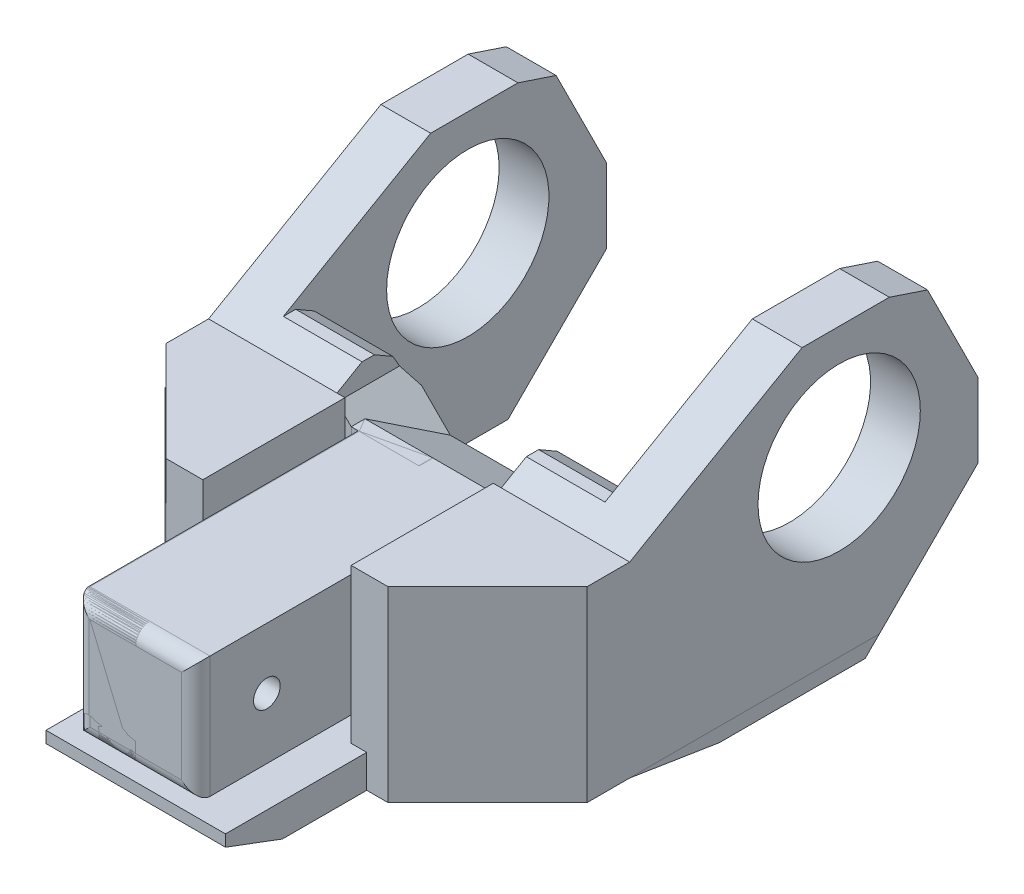
SolidWorks part; units mm, degrees
note: The reader was unsure of these and kept them because the rebuilt part matched: shared geometry of "Sketch1<4>".
ref_plane "Front Plane" through (0, 0, 0) normal (0, 0, 1) x (1, 0, 0)
ref_plane "Top Plane" through (0, 0, 0) normal (0, 1, 0) x (1, 0, 0)
ref_plane "Right Plane" through (0, 0, 0) normal (1, 0, 0) x (0, 0, -1)
sketch "Sketch1" plane through (0, 0, 0) normal (0, 1, 0) x (1, 0, 0)
  line L2 (0, 0) -> (0, 40)
  line L3 (0, 40) -> (21.59, 40)
  line L4 (21.59, 0) -> (21.59, 40)
  line L5 (-1.5, 40) -> (23.09, 40)
  line L6 (-1.5, 40) -> (-1.5, 45)
  line L7 (-1.5, 45) -> (23.09, 45)
  line L8 (23.09, 40) -> (23.09, 45)
  line L10 (0, 0) -> (0, -10.6333)
  line L11 (0, -10.6333) -> (21.59, -10.6333)
  line L12 (21.59, 0) -> (21.59, -10.6333)
  dimension "D1" = 21.59
  dimension "D3" = 1.5
  dimension "D4" = 1.5
  dimension "D5" = 5
extrude "Boss-Extrude1" add sketch "Sketch1" along normal blind 21.73
extrude "Boss-Extrude2" add sketch "Sketch1<4>" against normal blind 1.5 and the other way blind 23.23 contours L5 L8 L7 L6 L3
sketch "Sketch1<4>" plane through (0, 0, 0) normal (0, 1, 0) x (1, 0, 0) same geometry as "Sketch1"
sketch "Sketch2" plane through (23.09, 0, 0) normal (1, 0, 0) x (0, 0, -1)
  line L0 (40, -1.5) -> (45, -1.5) construction
  line L1 (40, 23.23) -> (59.05, 23.23)
  line L2 (40, 23.23) -> (40, -1.5)
  line L3 (40, -1.5) -> (59.05, -1.5)
  line L4 (59.05, 23.23) -> (59.05, -1.5)
  dimension "D1" = 19.05
extrude "Boss-Extrude3" add sketch "Sketch2" along normal blind 25.4
sketch "Sketch3" plane through (0, 0, -59.05) normal (0, 0, -1) x (-1, 0, 0)
  line L0 (-48.49, -1.5) -> (-23.09, -1.5) construction
  line L1 (-48.49, 23.23) -> (-42.14, 23.23)
  line L2 (-48.49, 23.23) -> (-48.49, -1.5)
  line L3 (-48.49, -1.5) -> (-42.14, -1.5)
  line L4 (-42.14, 23.23) -> (-42.14, -1.5)
  dimension "D1" = 6.35
extrude "Boss-Extrude4" add sketch "Sketch3" along normal blind 43.18
sketch "Sketch4" plane through (0, 0, -59.05) normal (0, 0, -1) x (-1, 0, 0)
  line L1 (-42.14, -1.5) -> (-23.09, -1.5)
  line L2 (-42.14, -1.5) -> (-42.14, 23.23)
  line L3 (-42.14, 23.23) -> (-23.09, 23.23)
  line L4 (-23.09, -1.5) -> (-23.09, 23.23)
extrude "Cut-Extrude1" cut sketch "Sketch4" against normal up to vertex (14.05 mm away)
sketch "Sketch5" plane through (0, 0, -45) normal (0, 0, -1) x (-1, 0, 0)
  line L1 (-42.14, 23.23) -> (1.5, 23.23)
  line L2 (-42.14, 23.23) -> (-42.14, -1.5)
  line L3 (-42.14, -1.5) -> (1.5, -1.5)
  line L4 (1.5, 23.23) -> (1.5, -1.5)
extrude "Boss-Extrude5" add sketch "Sketch5" along normal blind 7.62
sketch "Sketch6" plane through (0, -1.5, 0) normal (0, -1, 0) x (1, 0, 0)
  line L0 (48.49, -40) -> (48.49, -102.23) construction
  line L1 (-1.5, -40) -> (48.49, -40)
  line L2 (-1.5, -40) -> (-1.5, -52.62)
  line L3 (-1.5, -52.62) -> (42.14, -52.62)
  line L4 (48.49, -40) -> (48.49, -46.27)
  line L6 (48.49, -102.23) -> (42.14, -102.23)
  line L7 (48.49, -102.23) -> (48.49, -46.27)
  line L9 (42.14, -102.23) -> (42.14, -52.62)
extrude "Boss-Extrude6" add sketch "Sketch6" along normal blind 8.79
sketch "Sketch7" plane through (0, 23.23, 0) normal (0, 1, 0) x (1, 0, 0)
  line L0 (48.49, 102.23) -> (48.49, 40) construction
  line L1 (-1.5, 40) -> (48.49, 40)
  line L2 (-1.5, 40) -> (-1.5, 52.62)
  line L3 (-1.5, 52.62) -> (42.14, 52.62)
  line L4 (48.49, 40) -> (48.49, 46.27)
  line L5 (-1.5, 52.62) -> (42.14, 52.62) construction
  line L7 (42.14, 102.23) -> (48.49, 102.23)
  line L8 (42.14, 102.23) -> (42.14, 52.62)
  line L10 (48.49, 102.23) -> (48.49, 46.27)
extrude "Boss-Extrude7" add sketch "Sketch7" along normal blind 20.22
sketch "Sketch9" plane through (42.14, 0, 0) normal (-1, 0, 0) x (0, 0, 1)
  line L1 (-102.23, 43.45) -> (-52.62, 43.45)
  line L2 (-102.23, 43.45) -> (-102.23, -10.29)
  line L3 (-102.23, -10.29) -> (-52.62, -10.29)
  line L4 (-52.62, 43.45) -> (-52.62, -10.29)
extrude "Boss-Extrude8" add sketch "Sketch9" along normal blind 2.54
sketch "Sketch10" plane through (39.6, 0, 0) normal (-1, 0, 0) x (0, 0, 1)
  line L0 (-77.425, 43.45) -> (-77.425, 23.13)
  line L1 (-52.62, 43.45) -> (-102.23, 43.45) construction
  circle A0 centre (-77.425, 23.13) radius 14.5
  dimension "D1" = 29
  dimension "D2" = 20.32
extrude "Cut-Extrude2" cut sketch "Sketch10" against normal blind 44.704
sketch "Sketch11" plane through (0, 0, 10.6333) normal (0, 0, 1) x (1, 0, 0)
  line L6 (0, 0) -> (21.59, 0) construction
  line L7 (0, 21.73) -> (0, 0) construction
  circle A0 centre (2.54, 2.54) radius 1.778
  dimension "D1" = 3.556
  dimension "D3" = 2.54
  dimension "D2" = 2.54
fillet "Fillet3" radius 2.54 4 edges at (10.795, 0, 10.6333) (0, 10.865, 10.6333) (10.795, 21.73, 10.6333) (21.59, 10.865, 10.6333)
chamfer "Chamfer1" distance 20.16 angle 45 1 edges at (44.045, -10.29, -102.23)
chamfer "Chamfer2" distance 20.32 distance2 10.16 1 edges at (44.045, 43.45, -102.23)
sketch "Sketch12" plane through (0, 0, -40) normal (0, 0, 1) x (1, 0, 0)
  line L0 (-1.5, 43.45) -> (-1.5, -10.29) construction
  line L1 (-1.5, 21.73) -> (21.73, 21.73)
  line L2 (-1.5, 21.73) -> (-1.5, 43.45)
  line L3 (-1.5, 43.45) -> (21.73, 43.45)
  line L4 (21.73, 21.73) -> (21.73, 43.45)
  line L5 (-1.5, 43.45) -> (48.49, 43.45) construction
extrude "Cut-Extrude4" cut sketch "Sketch12" against normal blind 23.114
sketch "Sketch13" plane through (21.73, 0, 0) normal (-1, 0, 0) x (0, 0, 1)
  line L1 (-52.62, 43.45) -> (-40, 43.45)
  line L2 (-52.62, 43.45) -> (-52.62, 21.73)
  line L3 (-52.62, 21.73) -> (-40, 21.73)
  line L4 (-40, 43.45) -> (-40, 21.73)
extrude "Cut-Extrude5" cut sketch "Sketch13" against normal blind 3.81
chamfer "Chamfer4" distance 2.54 angle 45 1 edges at (25.54, 21.73, -46.31)
chamfer "Chamfer7" distance 17.78 angle 60 1 edges at (37.015, 43.45, -40)
chamfer "Chamfer8" distance 2.54 angle 81 1 edges at (23.495, -10.29, -40)
chamfer "Chamfer10" distance 12.7 distance2 6.35 1 edges at (39.6, 11.6037, -52.62)
sketch "Sketch16" plane through (0, 0, -40) normal (0, 0, 1) x (1, 0, 0)
  line L0 (-1.5, -7.75) -> (48.49, -7.75) construction
  line L1 (48.49, 25.67) -> (26.9, 25.67)
  line L2 (48.49, 25.67) -> (48.49, -7.75)
  line L3 (48.49, -7.75) -> (26.9, -7.75)
  line L4 (26.9, 25.67) -> (26.9, -7.75)
  dimension "D1" = 21.59
extrude "Boss-Extrude9" add sketch "Sketch16" along normal blind 25.4
sketch "Sketch17" plane through (-1.5, 0, 0) normal (-1, 0, 0) x (0, 0, 1)
  line L0 (-52.62, 21.73) -> (-52.62, -9.7488)
  line L1 (-52.62, -9.7488) -> (-40, -7.75)
  line L2 (-40, -7.75) -> (-40, 21.73)
  line L3 (-40, 21.73) -> (-52.62, 21.73)
extrude "Boss-Extrude10" add sketch "Sketch17" along normal blind 25.4
chamfer "Chamfer12" distance 5.08 distance2 10.16 1 edges at (-1.95, 21.73, -52.62)
chamfer "Chamfer13" distance 2.54 angle 45 1 edges at (44.045, 43.45, -92.07)
sketch "Sketch18" plane through (0, 0, -40) normal (0, 0, 1) x (1, 0, 0)
  line L0 (-26.9, 21.73) -> (0, 21.73) construction
  line L1 (-26.9, -7.75) -> (-2.77, -7.75)
  line L2 (-26.9, -7.75) -> (-26.9, 21.73)
  line L3 (-26.9, 21.73) -> (-2.77, 21.73)
  line L4 (-2.77, -7.75) -> (-2.77, 21.73)
  dimension "D1" = 24.13
extrude "Boss-Extrude11" add sketch "Sketch18" along normal blind 25.4
extrude "Cut-Extrude9" cut sketch "Sketch11" against normal through all
chamfer "Chamfer14" distance 17.78 angle 45 2 edges at (48.49, 8.96, -14.6) (-26.9, 6.99, -14.6)
sketch "Sketch19" plane through (0, 0, -40) normal (0, 0, 1) x (1, 0, 0)
  line L0 (26.9, 25.67) -> (26.9, -7.75) construction
  line L1 (-2.77, -7.75) -> (26.9, -7.75)
  line L2 (-2.77, -7.75) -> (-2.77, -2.67)
  line L3 (-2.77, -2.67) -> (26.9, -2.67)
  line L4 (26.9, -7.75) -> (26.9, -2.67)
  dimension "D1" = 5.08
extrude "Boss-Extrude12" add sketch "Sketch19" along normal through all
chamfer "Chamfer15" distance 10.16 distance2 3.81 1 edges at (12.065, -7.75, 10.6333)
sketch "Sketch20" plane through (0, 0, 0) normal (-1, 0, 0) x (0, 0, 1)
  line L0 (8.0933, 21.73) -> (-2.0667, 21.73)
  line L1 (8.0933, 21.73) -> (-40, 21.73) construction
  line L2 (-2.0667, 21.73) -> (-2.0667, 10.865)
  line L3 (-2.0667, 10.865) -> (8.0933, 10.865)
  line L4 (8.0933, 0) -> (8.0933, 21.73) construction
  circle A0 centre (-2.0667, 10.865) radius 2.3812
  dimension "D1" = 4.7625
  dimension "D2" = 10.16
extrude "Cut-Extrude10" cut sketch "Sketch20" against normal through all contours L2 A0 L3 | L3 A0 L2
sketch "Sketch21" plane through (0, 0, -40) normal (0, 0, -1) x (-1, 0, 0)
  line L1 (2.77, 21.73) -> (26.9, 21.73)
  line L2 (2.77, 21.73) -> (2.77, 18.7814)
  line L3 (2.77, 18.7814) -> (26.9, 18.7814)
  line L4 (26.9, 21.73) -> (26.9, 18.7814)
extrude "Cut-Extrude11" cut sketch "Sketch21" against normal up to surface (25.4 mm away) up to face at (-5.31, 5.058, -14.6)
sketch "Sketch22" plane through (-26.9, 0, 0) normal (-1, 0, 0) x (0, 0, 1)
  line L0 (-40, 18.7814) -> (-52.62, 10.0359)
  line L1 (-52.62, 16.65) -> (-52.62, -9.7488) construction
  line L2 (-52.62, 10.0359) -> (-52.62, 16.65)
  line L3 (-52.62, 16.65) -> (-40, 18.7814)
extrude "Cut-Extrude12" [suppressed] cut sketch "Sketch22" against normal up to surface (50.13 mm away)
ref_plane "Plane2" through (0, -7.75, 0) normal (0, -1, 0) x (-1, 0, 0)
split "Split1" trim tools "Plane2" bodies to split 124 resulting bodies 126 127
sketch "Sketch23" plane through (0, 21.73, 0) normal (0, 1, 0) x (1, 0, 0)
  line L0 (10.795, -8.0933) -> (10.795, 44.5675)
  line L1 (0, -8.0933) -> (21.59, -8.0933) construction
  line L2 (23, 50.67) -> (6.58, 42.46) construction
split line "Split Line1"
ref_plane "Plane3" through (10.865, 0, 0) normal (-1, 0, 0) x (0, 0, 1)
split "Split2" trim tools "Plane3" bodies to split 128 resulting bodies 129 130
mirror "Mirror2" about plane through (10.865, 0, 0) normal (-1, 0, 0) of bodies 129
combine bodies "Combine1" operation type add bodies to combine 131 129
sketch "Sketch24" plane through (0, 1.932, 1.1154) normal (0, 0.866, 0.5) x (1, 0, 0)
  line L0 (-3.81, 62.0483) -> (-3.81, 56.4603)
  line L1 (-3.81, 47.476) -> (-3.81, 62.0483) construction
  line L2 (-3.81, 56.4603) -> (-17.87, 56.4603)
  line L3 (-17.87, 56.4603) -> (-17.87, 69.3807)
  line L4 (-17.87, 69.3807) -> (-5.17, 62.0483)
  line L5 (-5.17, 62.0483) -> (-3.81, 62.0483)
  dimension "D1" = 5.588
extrude "Cut-Extrude13" cut sketch "Sketch24" against normal blind 26.67
mirror "Mirror3" about plane through (10.865, 0, 0) normal (-1, 0, 0) of "Cut-Extrude13"
sketch "Sketch25" plane through (25.54, 0, 0) normal (1, 0, 0) x (0, 0, -1)
  line L0 (52.62, 21.7802) -> (51.1825, 24.27)
  line L1 (51.1825, 24.27) -> (52.62, 24.27)
  line L2 (52.62, 24.27) -> (52.62, 21.7802)
extrude "Cut-Extrude14" cut sketch "Sketch25" against normal blind 31.496
chamfer "Chamfer17" distance 2.54 angle 60 1 edges at (32.57, 30.1622, -47.7807)
chamfer "Chamfer18" distance 2.54 angle 60 1 edges at (-10.84, 30.1622, -47.7807)
chamfer "Chamfer19" distance 1.27 2 edges at (-10.84, 28.8922, -45.5809) (32.57, 28.8922, -45.5809)
ref_plane "Plane4" through (10.865, 0, 0) normal (-1, 0, 0) x (0, 0, 1)
sketch "Sketch26" plane through (26.9, 0, 0) normal (-1, 0, 0) x (0, 0, 1)
  line L1 (-14.6, 25.67) -> (-40, 25.67)
  line L2 (-14.6, 25.67) -> (-14.6, -2.67)
  line L3 (-14.6, -2.67) -> (-40, -2.67)
  line L4 (-40, 25.67) -> (-40, -2.67)
extrude "Boss-Extrude13" add sketch "Sketch26" along normal blind 2.7856
mirror "Mirror4" about plane through (10.865, 0, 0) normal (-1, 0, 0) of "Boss-Extrude13"
sketch "Sketch27" plane through (0, -2.67, 0) normal (0, 1, 0) x (1, 0, 0)
  line L0 (24.1144, 14.6) -> (26.9, 14.6)
  line L1 (-2.3844, 40) -> (24.1144, 40)
  line L2 (-2.3844, 40) -> (-2.3844, 14.6)
  line L4 (24.1144, 40) -> (24.1144, 14.6)
  line L5 (-5.17, 14.6) -> (-2.3844, 14.6)
  line L6 (-5.17, 14.6) -> (-5.17, -10.6333)
  line L7 (-5.17, -10.6333) -> (26.9, -10.6333)
  line L8 (26.9, 14.6) -> (26.9, -10.6333)
extrude "Boss-Extrude14" add sketch "Sketch27" along normal blind 0.8
sketch "Sketch28" plane through (0, 0, 10.6333) normal (0, 0, 1) x (1, 0, 0)
  line L0 (19.05, 2.54) -> (2.68, 2.54) construction
  circle A0 centre (10.865, 2.54) radius 1.778
  dimension "D1" = 3.556
extrude "Cut-Extrude15" [suppressed] cut sketch "Sketch28" against normal through all
chamfer "Chamfer20" [suppressed] distance 0.254 angle 89
ref_plane "Plane5" through (9.8097, 0, -55.6335) normal (0.1736, 0, -0.9848) x (0, -1, 0)
sketch "Sketch30" plane through (9.8097, 0, -55.6335) normal (0.1736, 0, -0.9848) x (0, -1, 0)
  circle A0 centre (-3.2694, -9.6955) radius 2.032
  dimension "D1" = 4.064
extrude "Cut-Extrude16" cut sketch "Sketch30" against normal through all contours A0
